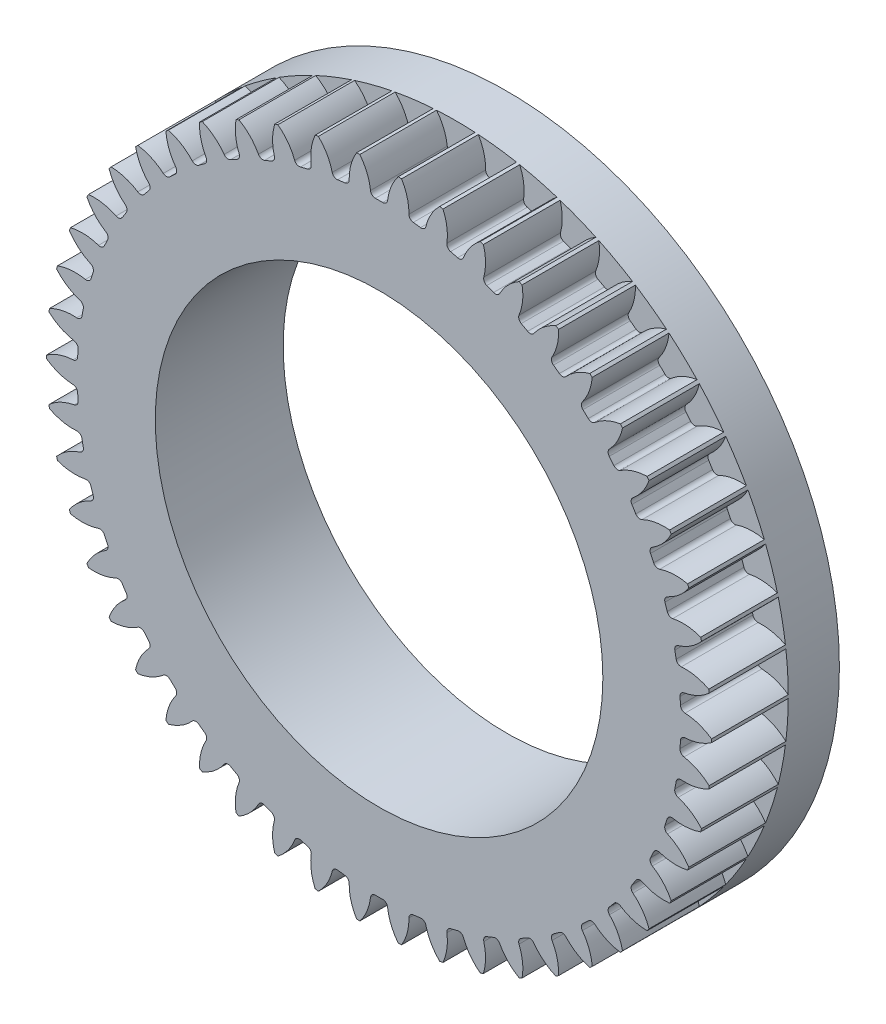
SolidWorks part; units mm, degrees
ref_plane "Front Plane" through (0, 0, 0) normal (0, 0, 1) x (1, 0, 0)
ref_plane "Top Plane" through (0, 0, 0) normal (0, 1, 0) x (1, 0, 0)
ref_plane "Right Plane" through (0, 0, 0) normal (1, 0, 0) x (0, 0, -1)
sketch "Sketch1" plane through (0, 0, 0) normal (0, 0, 1) x (1, 0, 0)
  line L0 (0, 0) -> (-18.1989, 0) construction
  line L1 (0, 0) -> (0, 8.2854) construction
  circle A0 centre (0, 0) radius 17.5
  circle A1 centre (0, 0) radius 26
  point P19 (0, 0)
  dimension "D1" = 35
  dimension "D2" = 52
extrude "Boss-Extrude1" add sketch "Sketch1" along normal blind 10
sketch "Sketch2" plane through (0, 0, 10) normal (0, 0, 1) x (1, 0, 0)
  line L0 (0, 0) -> (0, 26) construction
  line L1 (-0.6432, 23.5912) -> (0, 0) construction
  line L2 (0, 22.4212) -> (0.5017, 21.0429) construction
  circle A0 centre (0, 0) radius 26 construction
  arc A1 (0.6432, 23.5912) -> (-0.6432, 23.5912) centre (0, 0) ccw
  arc A2 (0.9352, 24.9825) -> (-0.9352, 24.9825) centre (0, 0) ccw construction
  arc A3 (-1.5041, 25.9565) -> (-0.6432, 23.5912) centre (-4.6208, 23.4828) cw
  arc A4 (1.5041, 25.9565) -> (0.6432, 23.5912) centre (4.6208, 23.4828) ccw
  point P16 (-0.8817, 24.8437)
  dimension "D1" = 50
  dimension "D2" = 2.4
  dimension "D3" = 20
  dimension "D4" = 1.8708
extrude "Cut-Extrude3" cut sketch "Sketch2" against normal blind 10 and the other way through all flip side to cut
fillet "Fillet1" radius 0.38 2 edges at (0.6432, 23.5912, 5) (-0.6432, 23.5912, 5)
pattern_circular "CirPattern1" count 50 over 360 about axis through (0, 0, 10) along (0, 0, 1) of "Cut-Extrude3", "Fillet1"
sketch "Sketch5" plane through (0, 0, 10) normal (0, 0, 1) x (1, 0, 0)
  line L0 (0, 17.5) -> (0, 32.5) construction
  circle A0 centre (0, 0) radius 17.5 construction
  circle A1 centre (0, 32.5) radius 1.5
  dimension "D2" = 3
  dimension "D1" = 15
sketch "Sketch6" plane through (0, 0, 0) normal (0, 0, 1) x (1, 0, 0)
  line L0 (0, 0) -> (-20.4531, 0) construction
  circle A0 centre (0, 0) radius 25
  dimension "D1" = 50
extrude "Cut-Extrude4" cut sketch "Sketch1<8>" along normal blind 4
sketch "Sketch1<8>" plane through (0, 0, 0) normal (0, 0, 1) x (1, 0, 0) same geometry as "Sketch1"
extrude "Boss-Extrude2" add sketch "Sketch1<9>" along normal blind 4
sketch "Sketch1<9>" plane through (0, 0, 0) normal (0, 0, 1) x (1, 0, 0) same geometry as "Sketch1"
equation "\"No. of teeth\"= 50"
equation "\"Module\"= 1mm"
equation "\"Bore Diameter\"= 35mm"
equation "\"Pressure Angle\"= 20"
equation "\"Outer Diameter\"= ( \"No. of teeth\" + 2 ) * \"Module\""
equation "\"Pitch Diameter\"= \"No. of teeth\" * \"Module\""
equation "\"Backlash\"= 0.3 * \"Module\""
equation "\"Are Length\"= ( ( \"Module\" * pi ) / 2 ) + \"Backlash\""
equation "\"Fillet Radius\"= 0.38 * \"Module\""
equation "\"Tooth Depth\"= IIF ( \"Module\" <= 1.25 , \"Module\" * 2.4 , \"Module\" * 2.25 )"
equation "\"D1@Sketch1\"=\"Bore Diameter\""
equation "\"D1@Sketch2\"=\"Pitch Diameter\""
equation "\"D2@Sketch2\"=\"Tooth Depth\""
equation "\"D3@Sketch2\"=\"Pressure Angle\""
equation "\"D4@Sketch2\"=\"Are Length\""
equation "\"D1@Fillet1\"=\"Fillet Radius\""
equation "\"D1@CirPattern1\"=\"No. of teeth\""
equation "\"D1@Sketch6\"=\"Pitch Diameter\""
